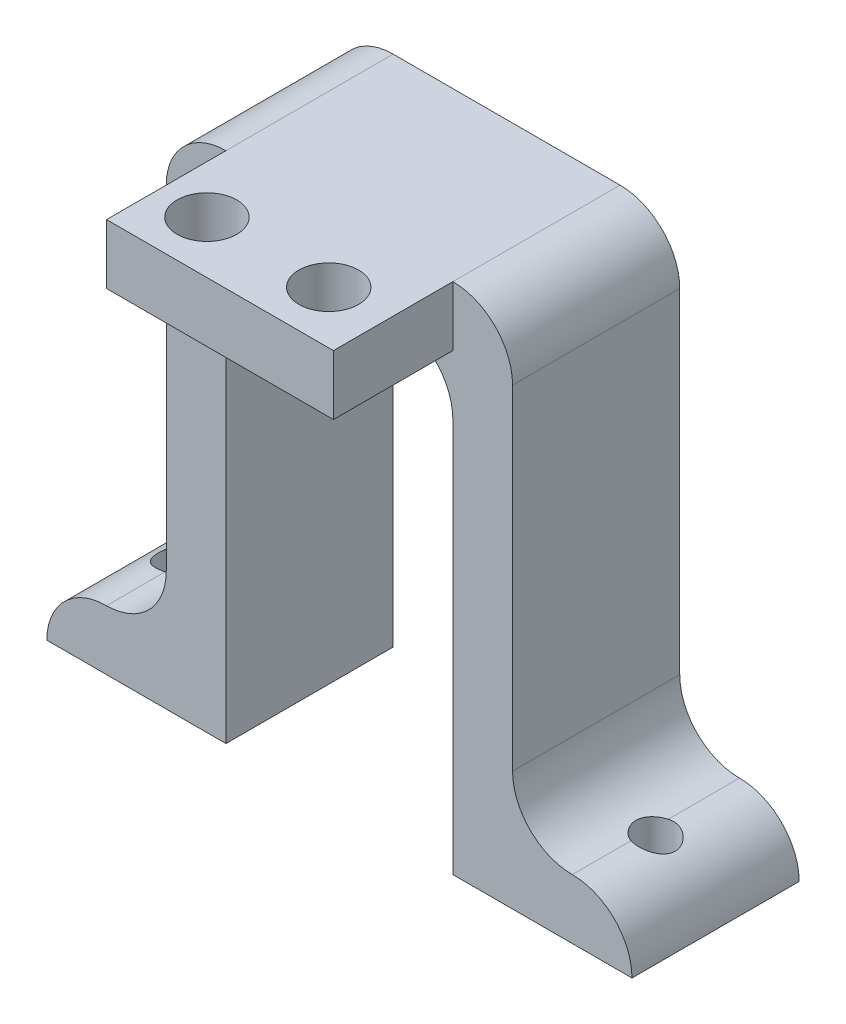
SolidWorks part; units mm, degrees
ref_plane "Front Plane" through (0, 0, 0) normal (0, 0, 1) x (1, 0, 0)
ref_plane "Top Plane" through (0, 0, 0) normal (0, 1, 0) x (1, 0, 0)
ref_plane "Right Plane" through (0, 0, 0) normal (1, 0, 0) x (0, 0, -1)
sketch "Sketch1" plane through (0, 0, 0) normal (0, 0, 1) x (1, 0, 0)
  line L0 (-24.5, 0) -> (-24.5, 5)
  line L1 (7.7, 0) -> (-7.7, 0) construction
  line L2 (-24.5, 5) -> (-14.5, 5)
  line L3 (-14.5, 5) -> (-14.5, 43)
  line L4 (-14.5, 43) -> (14.5, 43)
  line L5 (-24.5, 0) -> (-9.5, 0)
  line L6 (-9.5, 0) -> (-9.5, 38)
  line L7 (-9.5, 38) -> (9.5, 38)
  line L8 (0, -16.5) -> (0, 16.5) construction
  line L9 (24.5, 0) -> (9.5, 0)
  line L10 (24.5, 0) -> (24.5, 5)
  line L11 (24.5, 5) -> (14.5, 5)
  line L12 (9.5, 0) -> (9.5, 38)
  line L13 (14.5, 5) -> (14.5, 43)
  point P7 (0, 38)
  point P19 (0, 43)
  dimension "D1" = 19
  dimension "D2" = 5
  dimension "D3" = 5
  dimension "D4" = 5
  dimension "D5" = 10
  dimension "D6" = 38
extrude "Boss-Extrude1" add sketch "Sketch1" along normal blind 14
fillet "Fillet1" radius 5 6 edges at (-14.5, 43, 7) (14.5, 43, 7) (24.5, 5, 7) (-24.5, 5, 7) (14.5, 5, 7) (-14.5, 5, 7)
fillet "Fillet2" radius 5 2 edges at (9.5, 38, 7) (-9.5, 38, 7)
sketch "Sketch2" plane through (0, 0, 0) normal (0, 1, 0) x (1, 0, 0)
  line L0 (0, -16.5) -> (0, 16.5) construction
  circle A0 centre (-20, -7.5233) radius 1.636
  circle A1 centre (20, -7.5233) radius 1.636
  dimension "D1" = 40
extrude "Cut-Extrude3" cut sketch "Sketch2" against normal blind 10 and the other way blind 10 contours A0 | A1
sketch "Sketch4" plane through (0, 0, 14) normal (0, 0, 1) x (1, 0, 0)
  line L1 (9.5, 43) -> (-9.5, 43)
  line L2 (9.5, 43) -> (9.5, 38)
  line L3 (9.5, 38) -> (-9.5, 38)
  line L4 (-9.5, 43) -> (-9.5, 38)
extrude "Boss-Extrude2" add sketch "Sketch4" along normal blind 10
sketch "Sketch5" plane through (0, 43, 0) normal (0, 1, 0) x (1, 0, 0)
  circle A0 centre (4.7058, -19.6015) radius 2.5
  circle A1 centre (-5.4774, -19.6181) radius 2.5
  dimension "D1" = 5
  dimension "D2" = 5
extrude "Cut-Extrude4" cut sketch "Sketch5" against normal blind 10
